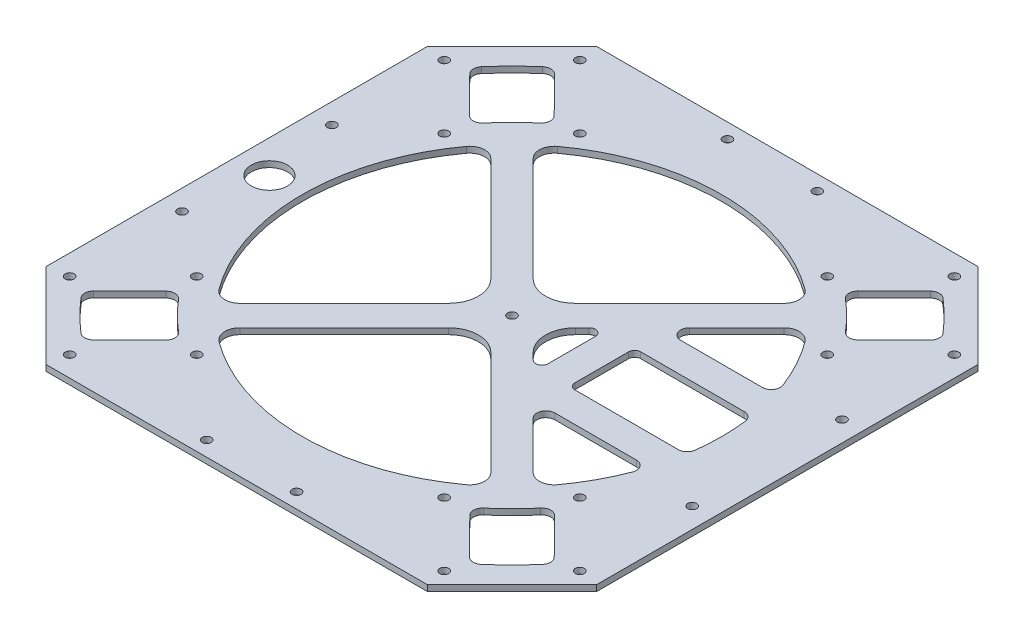
SolidWorks part; units mm, degrees
material "Thornel Mat VMA"
ref_plane "前视基准面" through (0, 0, 0) normal (0, 0, 1) x (1, 0, 0)
ref_plane "上视基准面" through (0, 0, 0) normal (0, 1, 0) x (1, 0, 0)
ref_plane "右视基准面" through (0, 0, 0) normal (1, 0, 0) x (0, 0, -1)
sketch "草图1" plane through (0, 0, 0) normal (0, 1, 0) x (1, 0, 0)
  line L0 (-63.6396, 91.9239) -> (-91.9239, 63.6396)
  line L1 (63.6396, 91.9239) -> (-63.6396, 91.9239)
  line L2 (91.9239, 63.6396) -> (91.9239, -63.6396)
  line L3 (63.6396, -91.9239) -> (-63.6396, -91.9239)
  line L4 (-91.9239, 63.6396) -> (-91.9239, -63.6396)
  line L5 (91.9239, 91.9239) -> (-91.9239, -91.9239) construction
  line L6 (91.9239, -91.9239) -> (-91.9239, 91.9239) construction
  line L7 (91.9239, -63.6396) -> (63.6396, -91.9239)
  line L8 (-91.9239, -63.6396) -> (-63.6396, -91.9239)
  line L9 (63.6396, 91.9239) -> (91.9239, 63.6396)
  line L10 (-91.9239, 91.9239) -> (-91.9239, -91.9239) construction
  line L11 (-91.9239, -91.9239) -> (91.9239, -91.9239) construction
  line L12 (91.9239, -91.9239) -> (91.9239, 91.9239) construction
  line L13 (91.9239, 91.9239) -> (-91.9239, 91.9239) construction
  point P0 (0, 0)
  dimension "D1" = 220
  dimension "D2" = 40
extrude "凸台-拉伸1" add sketch "草图1" along normal blind 2
sketch "草图11" plane through (0, 2, 0) normal (0, 1, 0) x (1, 0, 0)
  circle A0 centre (0, 0) radius 70
  dimension "D1" = 140
extrude "切除-拉伸6" cut sketch "草图11" against normal through all both and the other way through all
hole_wizard "孔1" positions "草图13" profile "草图14" legacy end condition through all
sketch "草图13" plane through (0, 0, 0) normal (0, -1, 0) x (-1, 0, 0)
  point P0 (85.1534, -62.5223)
  point P3 (63.9402, -41.3091)
  point P6 (41.3127, -63.9365)
  point P9 (62.5259, -85.1497)
  point P12 (-62.5259, -85.1497)
  point P15 (-41.3127, -63.9365)
  point P18 (-63.9402, -41.3091)
  point P21 (-85.1534, -62.5223)
  point P24 (-85.1534, 62.5296)
  point P27 (-62.5259, 85.157)
  point P30 (-41.3127, 63.9438)
  point P33 (-63.9402, 41.3164)
  point P36 (85.1534, 62.5296)
  point P39 (63.9402, 41.3164)
  point P42 (41.3127, 63.9438)
  point P45 (62.5259, 85.157)
sketch "草图14" plane through (-85.1534, 0, 62.5223) normal (1, 0, 0) x (0, 0, -1)
  line L0 (0, 0) -> (0, 2)
  line L1 (0, 2) -> (1.5, 2)
  line L2 (1.5, 2) -> (1.5, 0)
  line L3 (1.5, 0) -> (0, 0)
  line L4 (0, 110) -> (0, -10) construction
  dimension "直径" = 3
  dimension "深度" = 2
sketch "草图15" plane through (0, 2, 0) normal (0, 1, 0) x (1, 0, 0)
  line L0 (-54.5847, 45.4949) -> (-58.1891, 38.9105)
  line L1 (42.968, -57.1116) -> (54.5847, -45.4949)
  line L2 (-42.968, 57.1116) -> (-34.497, 60.9094)
  line L3 (57.1116, 42.968) -> (60.9094, 34.497)
  line L4 (57.1116, 42.968) -> (45.4949, 54.5847)
  line L5 (45.4949, 54.5847) -> (38.9105, 58.1891)
  line L6 (42.968, -57.1116) -> (34.497, -60.9094)
  line L7 (42.968, -57.1116) -> (54.5847, -45.4949)
  line L8 (-57.1116, -42.968) -> (-45.4949, -54.5847)
  line L9 (54.5847, -45.4949) -> (58.1891, -38.9105)
  line L10 (-57.1116, -42.968) -> (-60.9094, -34.497)
  line L11 (-57.1116, -42.968) -> (-45.4949, -54.5847)
  line L12 (-45.4949, -54.5847) -> (-38.9105, -58.1891)
  line L14 (-42.968, 57.1116) -> (-54.5847, 45.4949)
  line L20 (57.1116, 42.968) -> (45.4949, 54.5847)
  line L27 (-14.1421, 7.0711) -> (-48.9503, 41.8792)
  line L30 (-14.1421, -7.0711) -> (-48.9503, -41.8792)
  line L31 (7.0711, 14.1421) -> (41.8792, 48.9503)
  line L33 (-7.0711, 14.1421) -> (-41.8792, 48.9503)
  line L36 (14.1421, -7.0711) -> (48.9503, -41.8792)
  line L42 (7.0711, -14.1421) -> (41.8792, -48.9503)
  line L48 (-7.0711, -14.1421) -> (-41.8792, -48.9503)
  line L49 (14.1421, 7.0711) -> (48.9503, 41.8792)
  arc A0 (-56.5232, 41.2932) -> (-58.1891, 38.9105) centre (0, 0) ccw
  arc A1 (-34.497, 60.9094) -> (-41.2932, 56.5232) centre (0, 0) ccw
  arc A2 (-41.2932, -56.5232) -> (-38.9105, -58.1891) centre (0, 0) ccw
  arc A3 (60.9094, 34.497) -> (56.5232, 41.2932) centre (0, 0) ccw
  arc A4 (41.2932, 56.5232) -> (38.9105, 58.1891) centre (0, 0) ccw
  arc A5 (34.497, -60.9094) -> (41.2932, -56.5232) centre (0, 0) ccw
  arc A6 (56.5232, -41.2932) -> (58.1891, -38.9105) centre (0, 0) ccw
  arc A7 (-60.9094, -34.497) -> (-56.5232, -41.2932) centre (0, 0) ccw
  arc A8 (-45.8355, -52.9066) -> (-38.9105, -58.1891) centre (0, 0) ccw
  arc A9 (60.9094, 34.497) -> (52.9066, 45.8355) centre (0, 0) ccw
  arc A10 (34.497, -60.9094) -> (45.8355, -52.9066) centre (0, 0) ccw
  arc A11 (52.9066, -45.8355) -> (58.1891, -38.9105) centre (0, 0) ccw
  arc A12 (7.0711, -14.1421) -> (-7.0711, -14.1421) centre (0, -21.2132) ccw
  arc A13 (14.1421, -7.0711) -> (14.1421, 7.0711) centre (21.2132, 0) cw
  arc A14 (7.0711, 14.1421) -> (-7.0711, 14.1421) centre (0, 21.2132) cw
  arc A15 (-14.1421, -7.0711) -> (-14.1421, 7.0711) centre (-21.2132, 0) ccw
  circle A16 centre (0, 0) radius 70 construction
  arc A17 (56.5232, -41.2932) -> (48.9503, -41.8792) centre (52.4858, -38.3437) cw
  arc A18 (41.8792, -48.9503) -> (41.2932, -56.5232) centre (38.3437, -52.4858) cw
  arc A19 (56.5232, 41.2932) -> (48.9503, 41.8792) centre (52.4858, 38.3437) ccw
  arc A20 (41.2932, 56.5232) -> (41.8792, 48.9503) centre (38.3437, 52.4858) cw
  arc A21 (-41.2932, 56.5232) -> (-41.8792, 48.9503) centre (-38.3437, 52.4858) ccw
  arc A22 (-48.9503, 41.8792) -> (-56.5232, 41.2932) centre (-52.4858, 38.3437) ccw
  arc A23 (-41.8792, -48.9503) -> (-41.2932, -56.5232) centre (-38.3437, -52.4858) ccw
  arc A24 (-48.9503, -41.8792) -> (-56.5232, -41.2932) centre (-52.4858, -38.3437) cw
  point P1 (0, 0)
  point P11 (0, 0)
  point P16 (0, 0)
  point P21 (0, 0)
  point P58 (0, 0)
  circle M25 centre (0, 0) radius 70
  dimension "D1" = 10
  dimension "D4" = 5
  dimension "D2" = 4
  dimension "D3" = 4
extrude "凸台-拉伸5" add sketch "草图15" against normal up to surface (2 mm away) contours A15 L30 L48 A12 L42 L36 A13 L49 L31 A14 L33 L27 M25 | L8 L12 L10 M25 | L1 L9 L6 M25 | L4 L5 L3 M25 | L2 L14 L0 M25 region at (-47.2019, 2, -51.7628) region at (0, 2, 0) region at (-51.7628, 2, 47.2019) region at (51.7628, 2, -47.2019) region at (47.2019, 2, 51.7628) up to face at (-85.1534, 0, 61.0223)
hole_wizard "孔2" positions "草图16" profile "草图17" legacy end condition through all
sketch "草图16" plane through (0, 0, 0) normal (0, -1, 0) x (-1, 0, 0)
  point P0 (0, 0)
sketch "草图17" plane through (0, 0, 0) normal (1, 0, 0) x (0, 0, -1)
  line L0 (0, 0) -> (0, 2)
  line L1 (0, 2) -> (1.5, 2)
  line L2 (1.5, 2) -> (1.5, 0)
  line L3 (1.5, 0) -> (0, 0)
  line L4 (0, 110) -> (0, -10) construction
  dimension "直径" = 3
  dimension "深度" = 2
sketch "草图20" plane through (0, 2, 0) normal (0, 1, 0) x (1, 0, 0)
  line L0 (55.8614, 55.8614) -> (77.7817, 77.7817) construction
  line L1 (64.8107, 50.7195) -> (76.9107, 62.7268)
  line L3 (50.7195, -64.8107) -> (62.7268, -76.9107)
  line L4 (50.6805, 64.8737) -> (62.7878, 76.8882)
  line L5 (62.453, 48.3799) -> (64.7375, 78.823) construction
  line L6 (78.8741, 64.6752) -> (48.3019, 62.5134) construction
  line L7 (64.8737, -50.6805) -> (76.8882, -62.7878)
  line L8 (55.8614, -55.8614) -> (77.7817, -77.7817) construction
  line L9 (48.3799, -62.453) -> (78.823, -64.7375) construction
  line L10 (64.6752, -78.8741) -> (62.5134, -48.3019) construction
  line L11 (-64.8107, -50.7195) -> (-76.9107, -62.7268)
  line L12 (-50.6805, -64.8737) -> (-62.7878, -76.8882)
  line L13 (-55.8614, -55.8614) -> (-77.7817, -77.7817) construction
  line L14 (-62.453, -48.3799) -> (-64.7375, -78.823) construction
  line L15 (-78.8741, -64.6752) -> (-48.3019, -62.5134) construction
  line L16 (-50.7195, 64.8107) -> (-62.7268, 76.9107)
  line L17 (-64.8737, 50.6805) -> (-76.8882, 62.7878)
  line L18 (-55.8614, 55.8614) -> (-77.7817, 77.7817) construction
  line L19 (-48.3799, 62.453) -> (-78.823, 64.7375) construction
  line L20 (-64.6752, 78.8741) -> (-62.5134, 48.3019) construction
  line L21 (91.9239, 63.6396) -> (63.6396, 91.9239) construction
  arc A0 (77.0641, 66.8216) -> (66.8676, 77.0242) centre (0, 0) ccw
  arc A1 (60.4037, 50.9155) -> (50.8621, 60.4487) centre (0, 0) ccw
  arc A3 (64.8107, 50.7195) -> (60.4037, 50.9155) centre (62.6976, 52.849) cw
  arc A4 (76.9107, 62.7268) -> (77.0641, 66.8216) centre (74.7975, 64.8562) ccw
  arc A5 (66.8676, 77.0242) -> (62.7878, 76.8882) centre (64.9009, 74.7588) ccw
  arc A6 (50.8621, 60.4487) -> (50.6805, 64.8737) centre (52.7936, 62.7442) cw
  arc A7 (66.8216, -77.0641) -> (77.0242, -66.8676) centre (0, 0) ccw
  arc A8 (50.9155, -60.4037) -> (60.4487, -50.8621) centre (0, 0) ccw
  arc A9 (50.7195, -64.8107) -> (50.9155, -60.4037) centre (52.849, -62.6976) cw
  arc A10 (62.7268, -76.9107) -> (66.8216, -77.0641) centre (64.8562, -74.7975) ccw
  arc A11 (77.0242, -66.8676) -> (76.8882, -62.7878) centre (74.7588, -64.9009) ccw
  arc A12 (60.4487, -50.8621) -> (64.8737, -50.6805) centre (62.7442, -52.7936) cw
  arc A13 (-77.0641, -66.8216) -> (-66.8676, -77.0242) centre (0, 0) ccw
  arc A14 (-60.4037, -50.9155) -> (-50.8621, -60.4487) centre (0, 0) ccw
  arc A15 (-64.8107, -50.7195) -> (-60.4037, -50.9155) centre (-62.6976, -52.849) cw
  arc A16 (-76.9107, -62.7268) -> (-77.0641, -66.8216) centre (-74.7975, -64.8562) ccw
  arc A17 (-66.8676, -77.0242) -> (-62.7878, -76.8882) centre (-64.9009, -74.7588) ccw
  arc A18 (-50.8621, -60.4487) -> (-50.6805, -64.8737) centre (-52.7936, -62.7442) cw
  arc A19 (-66.8216, 77.0641) -> (-77.0242, 66.8676) centre (0, 0) ccw
  arc A20 (-50.9155, 60.4037) -> (-60.4487, 50.8621) centre (0, 0) ccw
  arc A21 (-50.7195, 64.8107) -> (-50.9155, 60.4037) centre (-52.849, 62.6976) cw
  arc A22 (-62.7268, 76.9107) -> (-66.8216, 77.0641) centre (-64.8562, 74.7975) ccw
  arc A23 (-77.0242, 66.8676) -> (-76.8882, 62.7878) centre (-74.7588, 64.9009) ccw
  arc A24 (-60.4487, 50.8621) -> (-64.8737, 50.6805) centre (-62.7442, 52.7936) cw
  point P4 (0, 0)
  point P5 (63.5947, 63.5947)
  point P23 (0, 0)
  point P24 (77.7817, 77.7817)
  point P26 (63.5947, -63.5947)
  point P45 (-63.5947, -63.5947)
  point P64 (-63.5947, 63.5947)
  point P82 (0, 0)
  dimension "D1" = 79
  dimension "D2" = 102
  dimension "D4" = 3
  dimension "D3" = 20
  dimension "D5" = 4
extrude "切除-拉伸7" cut sketch "草图20" against normal through all both and the other way through all
sketch "草图21" plane through (0, 2, 0) normal (0, 1, 0) x (1, 0, 0)
  line L0 (-91.9239, 0) -> (-70, 0) construction
  line L1 (-91.9239, 63.6396) -> (-91.9239, -63.6396) construction
  circle A0 centre (-80.9686, 0) radius 6.05
  arc A1 (-56.5232, 41.2932) -> (-56.5232, -41.2932) centre (0, 0) ccw construction
  point P9 (0, 0)
  dimension "D1" = 12.1
extrude "切除-拉伸8" cut sketch "草图21" against normal through all both and the other way through all
sketch "草图22" plane through (0, 2, 0) normal (0, 1, 0) x (1, 0, 0)
  line L0 (0, 91.9239) -> (0, -91.9239) construction
  line L1 (63.6396, 91.9239) -> (-63.6396, 91.9239) construction
  line L2 (-63.6396, -91.9239) -> (63.6396, -91.9239) construction
  line L3 (85.1534, 62.5296) -> (85.1534, -62.5223) construction
  line L4 (15, 86.9239) -> (-15, 86.9239)
  line L5 (15, 86.9239) -> (15, -86.9239)
  line L6 (15, -86.9239) -> (-15, -86.9239)
  line L7 (-15, 86.9239) -> (-15, -86.9239)
  line L8 (15, 86.9239) -> (-15, -86.9239) construction
  line L9 (15, -86.9239) -> (-15, 86.9239) construction
  line L10 (-85.1534, 25) -> (85.1534, 25)
  line L11 (-85.1534, 25) -> (-85.1534, -25)
  line L12 (-85.1534, -25) -> (85.1534, -25)
  line L13 (85.1534, 25) -> (85.1534, -25)
  line L14 (-85.1534, 25) -> (85.1534, -25) construction
  line L15 (-85.1534, -25) -> (85.1534, 25) construction
  point P6 (0, 0)
  point P12 (0, 0)
  point P22 (85.1534, -18.4563)
  dimension "D1" = 30
  dimension "D2" = 5
  dimension "D3" = 50
hole_wizard "孔4" positions "草图23" profile "草图24" legacy end condition through all
sketch "草图23" plane through (0, 2, 0) normal (0, 1, 0) x (1, 0, 0)
  point P0 (-15, -86.9239)
  point P3 (15, -86.9239)
  point P6 (-15, 86.9239)
  point P9 (15, 86.9239)
  point P12 (-85.1534, 25)
  point P15 (-85.1534, -25)
  point P18 (85.1534, 25)
  point P21 (85.1534, -25)
sketch "草图24" plane through (-15, 2, 86.9239) normal (1, 0, 0) x (0, 0, 1)
  line L0 (0, 0) -> (0, 2)
  line L1 (0, 2) -> (1.5, 2)
  line L2 (1.5, 2) -> (1.5, 0)
  line L3 (1.5, 0) -> (0, 0)
  line L4 (0, 110) -> (0, -10) construction
  dimension "直径" = 3
  dimension "深度" = 2
sketch "草图25" plane through (0, 0, 0) normal (0, -1, 0) x (-1, 0, 0)
  line L0 (-35.3137, -21) -> (-62.554, -21)
  line L1 (-48.9503, -41.8792) -> (-14.1421, -7.0711) construction
  line L2 (-22.95, -21) -> (-81.05, -21) construction
  line L3 (-35.5633, 28.4923) -> (-33.1924, 26.1213)
  line L4 (-66.5207, -11) -> (-31.95, -11)
  line L5 (-16.4055, -9.3344) -> (-14.021, -6.9499)
  line L6 (-14.021, -6.9499) -> (-12.0262, -9.8724)
  line L7 (-12.0262, -9.8724) -> (-34.9991, -29.1641)
  line L8 (-34.9991, -29.1641) -> (-35.5633, -28.4923)
  line L9 (-35.5633, -28.4923) -> (-33.1924, -26.1213)
  line L10 (0, 0) -> (-75.6878, 0) construction
  line L11 (-34.9991, 29.1641) -> (-35.5633, 28.4923)
  line L12 (-12.0262, 9.8724) -> (-34.9991, 29.1641)
  line L13 (-14.021, 6.9499) -> (-12.0262, 9.8724)
  line L14 (-16.4055, 9.3344) -> (-14.021, 6.9499)
  line L15 (-66.5207, 11) -> (-31.95, 11)
  line L16 (-35.3137, 21) -> (-62.554, 21)
  line L17 (-19.95, 7.8662) -> (-19.95, -7.8662)
  line L18 (-19.95, 18) -> (-19.95, -18) construction
  line L20 (-29.95, -9) -> (-29.95, 9)
  arc A0 (-65.3549, 25.0746) -> (-69.4992, 8.3582) centre (0, 0) ccw
  arc A1 (-56.5232, 41.2932) -> (-56.5232, -41.2932) centre (0, 0) ccw construction
  arc A2 (-31.95, 11) -> (-29.95, 9) centre (-31.95, 9) cw
  arc A3 (-35.3137, -21) -> (-33.1924, -26.1213) centre (-35.3137, -24) cw
  arc A4 (-69.4992, -8.3582) -> (-66.5207, -11) centre (-66.5207, -8) ccw
  arc A5 (-65.3549, -25.0746) -> (-62.554, -21) centre (-62.554, -24) cw
  arc A6 (-65.3549, 25.0746) -> (-62.554, 21) centre (-62.554, 24) ccw
  arc A7 (-69.4992, 8.3582) -> (-66.5207, 11) centre (-66.5207, 8) cw
  arc A8 (-35.3137, 21) -> (-33.1924, 26.1213) centre (-35.3137, 24) ccw
  arc A9 (-31.95, -11) -> (-29.95, -9) centre (-31.95, -9) ccw
  arc A10 (-16.4055, 9.3344) -> (-19.95, 7.8662) centre (-17.8737, 7.8662) ccw
  arc A11 (-19.95, -7.8662) -> (-16.4055, -9.3344) centre (-17.8737, -7.8662) ccw
  arc A12 (-65.3549, 25.0746) -> (-69.4992, 8.3582) centre (0, 0) ccw
  arc A13 (-69.4992, -8.3582) -> (-65.3549, -25.0746) centre (0, 0) ccw
  point P18 (-18.0711, -11)
  point P21 (-28.0711, -21)
  point P42 (-28.0711, 21)
  point P43 (-18.0711, 11)
  point P48 (-29.95, 11)
  point P51 (-29.95, -11)
  point P56 (-19.95, 12.8789)
  point P59 (-19.95, -12.8789)
  dimension "D1" = 10
  dimension "D3" = 2
  dimension "D4" = 2.0763
  dimension "D2" = 10
extrude "凸台-拉伸6" add sketch "草图25" against normal blind 2 contours L17 L10 L20 A9 L4 A4 A13 A5 L0 A3 L9 L8 L7 L6 L5 A11 | L10 L17 A10 L14 L13 L12 L11 L3 A8 L16 A6 A0 A7 L15 A2 L20 region at (39.3616, 0, 14.2119) region at (39.3616, 0, -14.2119)
